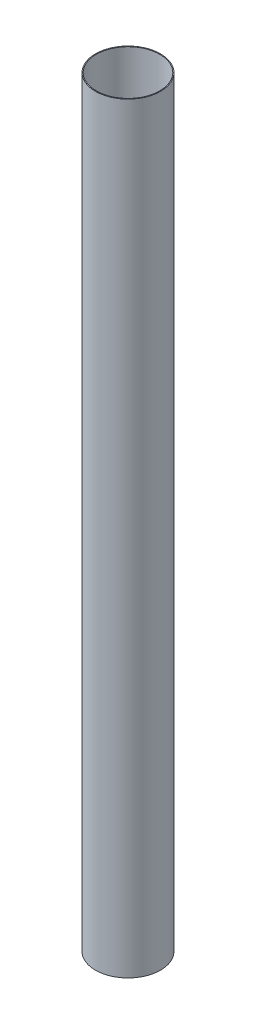
SolidWorks part; units mm, degrees
material "Hexcel AS4C (3000 Filaments)"
ref_plane "Front Plane" through (0, 0, 0) normal (0, 0, 1) x (1, 0, 0)
ref_plane "Top Plane" through (0, 0, 0) normal (0, 1, 0) x (1, 0, 0)
ref_plane "Right Plane" through (0, 0, 0) normal (1, 0, 0) x (0, 0, -1)
sketch "Sketch1" plane through (0, 0, 0) normal (0, 1, 0) x (1, 0, 0)
  circle A0 centre (0, 0) radius 63.5
  circle A1 centre (0, 0) radius 65.151
  dimension "D1" = 127
  dimension "D2" = 130.302
extrude "Boss-Extrude1" add sketch "Sketch1" along normal blind 1524
